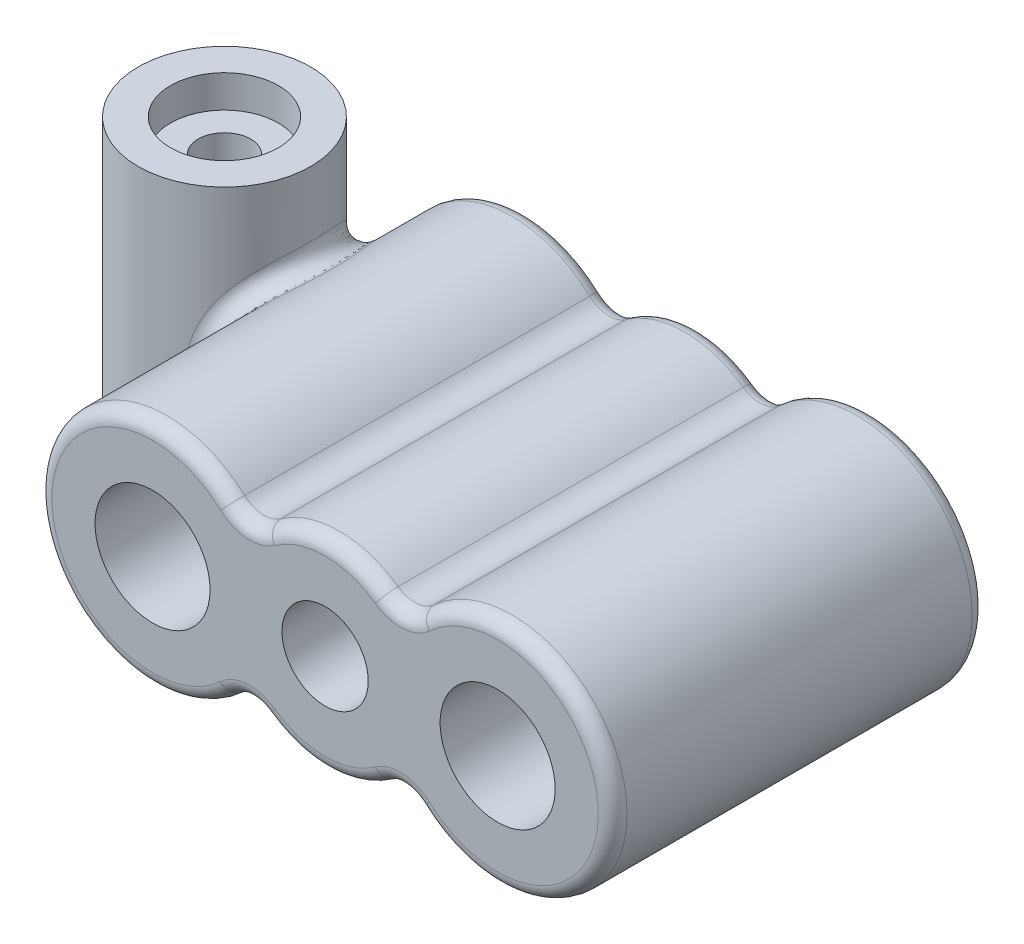
SolidWorks part; units mm, degrees
ref_plane "Front Plane" through (0, 0, 0) normal (0, 0, 1) x (1, 0, 0)
ref_plane "Top Plane" through (0, 0, 0) normal (0, 1, 0) x (1, 0, 0)
ref_plane "Right Plane" through (0, 0, 0) normal (1, 0, 0) x (0, 0, -1)
sketch "Sketch19" plane through (0, 0, 0) normal (0, 0, 1) x (1, 0, 0)
  circle A0 centre (0, 0) radius 11.176
  circle A1 centre (-19.05, 0) radius 12.7
  circle A2 centre (19.05, 0) radius 12.7
  dimension "D1" = 25.4
  dimension "D2" = 25.4
  dimension "D3" = 22.352
  dimension "D4" = 19.05
  dimension "D5" = 38.1
extrude "Boss-Extrude3" add sketch "Sketch19" along normal mid plane 41.275 contours A0 A1 | A2 A0 A1 | A0 A1 | A0 A2 | A0 A2 region at (8.7305, 0, 0) region at (20.1102, 0, 0) region at (0, 0, 0) region at (-8.7305, 0, 0) region at (-20.1102, 0, 0)
fillet "Fillet6" radius 3.175 4 edges at (8.57, -7.1735, 0) (-8.57, -7.1735, 0) (8.57, 7.1735, 0) (-8.57, 7.1735, 0)
fillet "Fillet7" radius 1.5875 16 edges at (-8.5134, 8.5271, 20.6375) (31.75, 0, 20.6375) (8.5134, -8.5271, 20.6375) (0, -11.176, 20.6375) (-8.5134, -8.5271, 20.6375) (8.5134, 8.5271, 20.6375) (0, 11.176, 20.6375) (-31.75, 0, 20.6375) (-8.5134, 8.5271, -20.6375) (0, 11.176, -20.6375) (8.5134, 8.5271, -20.6375) (31.75, 0, -20.6375) (8.5134, -8.5271, -20.6375) (0, -11.176, -20.6375) (-8.5134, -8.5271, -20.6375) (-31.75, 0, -20.6375)
sketch "Sketch20" plane through (0, 0, 0) normal (0, 1, 0) x (1, 0, 0)
  line L0 (-11.5362, 20.6375) -> (-30.1625, 20.6375) construction
  circle A0 centre (-38.1, 6.35) radius 9.525
  dimension "D1" = 14.2875
  dimension "D2" = 19.05
  dimension "D3" = 38.1
extrude "Boss-Extrude4" add sketch "Sketch20" along normal mid plane 38.1
fillet "Fillet8" radius 1.5875 1 edges at (-31.6955, -1.1751, -13.4004)
hole_wizard "CBORE for #12 Binding Head Machine Screw1" positions "Sketch21" profile "Sketch22" counterbore size "#12" standard "ANSI Inch" end condition through all
sketch "Sketch21" plane through (0, 19.05, 0) normal (0, 1, 0) x (1, 0, 0)
  point P0 (-38.1, 6.35)
sketch "Sketch22" plane through (-38.1, 19.05, -6.35) normal (1, 0, 0) x (0, 0, 1)
  line L0 (0, 0) -> (0, 38.1)
  line L1 (0, 38.1) -> (2.8956, 38.1)
  line L3 (2.8956, 38.1) -> (2.8956, 3.5814)
  line L4 (2.8956, 3.5814) -> (5.9538, 3.5814)
  line L5 (5.9538, 3.5814) -> (5.9538, 0)
  line L7 (5.9538, 0) -> (0, 0)
  line L11 (0, -6.35) -> (0, 107.95) construction
  dimension "Thru Hole Dia." = 5.7912
  dimension "Thru Hole Depth" = 38.1
  dimension "C'Bore Dia." = 11.9075
  dimension "C'Bore Depth" = 3.5814
hole_wizard "#97 (0.5) Diameter Hole1" positions "Sketch25" profile "Sketch24" hole size "#97" standard "ANSI Inch" end condition through all
sketch "Sketch25" plane through (0, 0, 20.6375) normal (0, 0, 1) x (1, 0, 0)
  point P0 (-19.05, 0)
  point P1 (19.05, 0)
  dimension "D1" = 38.1
  dimension "D2" = 19.05
sketch "Sketch24" plane through (-19.05, 0, 20.6375) normal (1, 0, 0) x (0, -1, 0)
  line L0 (0, 0) -> (0, 41.275)
  line L1 (0, 41.275) -> (6.35, 41.275)
  line L2 (6.35, 41.275) -> (6.35, 0)
  line L5 (6.35, 0) -> (0, 0)
  line L11 (0, -6.35) -> (0, 107.95) construction
  dimension "Thru Hole Dia." = 12.7
  dimension "Thru Hole Depth" = 41.275
hole_wizard "#97 (0.375) Diameter Hole1" positions "Sketch26" profile "Sketch27" hole size "#97" standard "ANSI Inch" end condition through all
sketch "Sketch26" plane through (0, 0, 20.6375) normal (0, 0, 1) x (1, 0, 0)
  point P0 (0, 0)
sketch "Sketch27" plane through (0, 0, 20.6375) normal (1, 0, 0) x (0, -1, 0)
  line L0 (0, 0) -> (0, 41.275)
  line L1 (0, 41.275) -> (4.7625, 41.275)
  line L2 (4.7625, 41.275) -> (4.7625, 0)
  line L5 (4.7625, 0) -> (0, 0)
  line L11 (0, -6.35) -> (0, 107.95) construction
  dimension "Thru Hole Dia." = 9.525
  dimension "Thru Hole Depth" = 41.275
